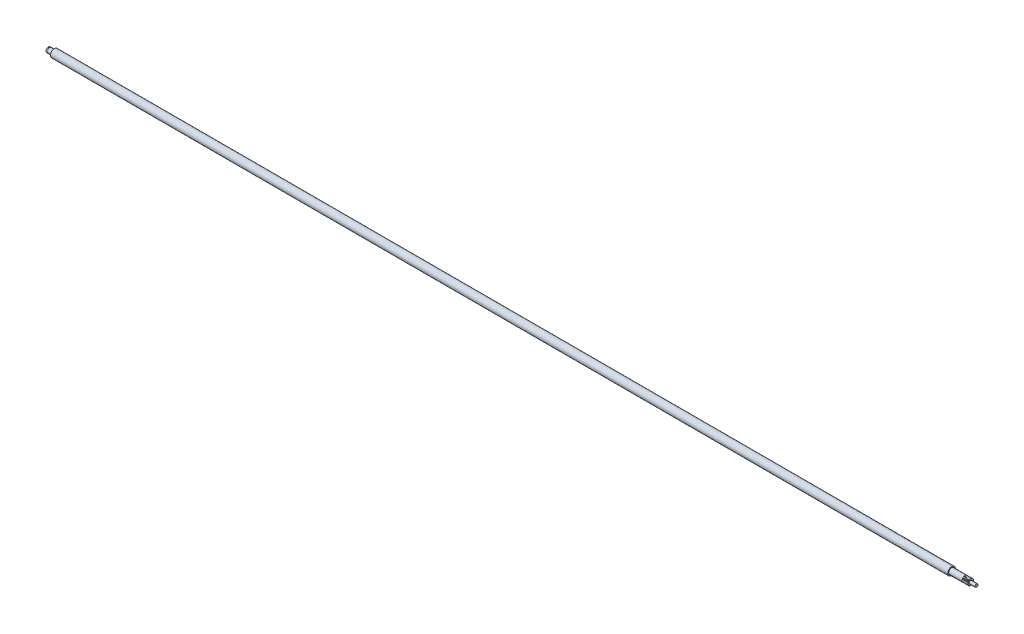
SolidWorks part; units mm, degrees
material "Хромистая нержавеющая сталь"
ref_plane "Спереди" through (0, 0, 0) normal (0, 0, 1) x (1, 0, 0)
ref_plane "Сверху" through (0, 0, 0) normal (0, 1, 0) x (1, 0, 0)
ref_plane "Справа" through (0, 0, 0) normal (1, 0, 0) x (0, 0, -1)
sketch "Эскиз1" plane through (0, 0, 0) normal (0, 0, 1) x (1, 0, 0)
  line L0 (-1813.0019, 5.9419) -> (-1813.0019, 10.9419)
  line L1 (-1813.0019, 10.9419) -> (-1811.3019, 10.9419)
  line L2 (-1811.3019, 10.9419) -> (-1811.3019, 10.7419)
  line L3 (-1811.3019, 10.7419) -> (-1810.1519, 10.7419)
  line L4 (-1810.1519, 10.7419) -> (-1810.1519, 10.9419)
  line L5 (-1810.1519, 10.9419) -> (-1801.0019, 10.9419)
  line L6 (-1801.0019, 10.9419) -> (-1801.0019, 13.9419)
  line L7 (-1801.0019, 13.9419) -> (35.9981, 13.9419)
  line L8 (35.9981, 13.9419) -> (35.9981, 11.9419)
  line L9 (35.9981, 11.9419) -> (74.9981, 11.9419)
  line L10 (74.9981, 11.9419) -> (74.9981, 8.9419)
  line L11 (74.9981, 8.9419) -> (86.9981, 8.9419)
  line L12 (86.9981, 8.9419) -> (86.9981, 5.9419)
  line L13 (86.9981, 5.9419) -> (-1813.0019, 5.9419)
  line L14 (62.9981, 14.6846) -> (62.9981, -1.3142) construction
  dimension "D1" = 1.15
  dimension "D2" = 9.15
  dimension "D3" = 12
  dimension "D4" = 39
  dimension "D5" = 51
  dimension "D6" = 12
  dimension "D7" = 3
  dimension "D8" = 3
  dimension "D9" = 2
  dimension "D10" = 5
  dimension "D11" = 4.8
  dimension "D12" = 5
  dimension "D13" = 1900
revolve "Повернуть1" add sketch "Эскиз1" angle 360 about L13
ref_plane "Плоскость1" through (45.9981, 0, 0) normal (1, 0, 0) x (0, 0, -1)
sketch "Эскиз2" plane through (45.9981, 0, 0) normal (1, 0, 0) x (0, 0, -1)
  circle A0 centre (0, 5.9419) radius 8 construction
  circle A1 centre (0, 5.9419) radius 8
curve "Спираль1" pitch 5 height 290 turns 58
sketch "Эскиз3" plane through (0, 0, 0) normal (0, 0, 1) x (1, 0, 0)
  line L0 (-207.8405, -2.5666) -> (-201.4949, -2.5666) construction
  line L1 (-210.2778, -2.0666) -> (-203.5838, -2.0666) construction
  line L2 (-207.8405, -4.8575) -> (-207.8405, -1.8666) construction
  line L3 (-205.3405, -4.8575) -> (-205.3405, -0.2923) construction
  line L4 (-205.3405, -1.8666) -> (-205.4905, -2.0666)
  line L5 (-205.4905, -2.0666) -> (-205.4905, -2.5666)
  line L6 (-205.4905, -2.5666) -> (-205.1905, -2.5666)
  line L7 (-205.1905, -2.5666) -> (-205.1905, -2.0666)
  line L8 (-205.1905, -2.0666) -> (-205.3405, -1.8666)
  circle A0 centre (-207.8405, -2.5666) radius 1.5875
  point P7 (-207.7498, -2.0666)
  dimension "D1" = 3.175
  dimension "D2" = 0.5
  dimension "D3" = 2.5
  dimension "D4" = 0.2
  dimension "D5" = 0.3
ref_plane "Плоскость2" through (84.9981, 0, 0) normal (1, 0, 0) x (0, 0, -1)
sketch "Эскиз4" plane through (84.9981, 0, 0) normal (1, 0, 0) x (0, 0, -1)
  circle A0 centre (0, 5.9419) radius 6 construction
  circle A1 centre (0, 5.9419) radius 6
curve "Спираль2" pitch 1 height 22 radius 6 centre (84.9981, 5.9419, 0) axis (-1, 0, 0) start towards (0, 0, 1)
sketch "Эскиз5" plane through (0, 0, 0) normal (0, 0, 1) x (1, 0, 0)
  line L0 (76.2561, 0.4419) -> (75.7561, -0.0581)
  line L1 (35.9981, -0.0581) -> (74.9981, -0.0581) construction
  line L2 (75.7561, -0.0581) -> (75.7561, -1.0581)
  line L3 (75.7561, -1.0581) -> (76.7561, -1.0581)
  line L4 (76.7561, -1.0581) -> (76.7561, -0.0581)
  line L5 (76.7561, -0.0581) -> (76.2561, 0.4419)
  line L6 (76.2561, 0.4419) -> (76.2561, -0.2584) construction
  line L7 (75.7561, -0.0581) -> (76.7561, -0.0581) construction
  dimension "D1" = 0.5
  dimension "D2" = 1
  dimension "D3" = 1
sweep "Вырез-По траектории7" cut profiles "Эскиз5" path "Спираль2" align with end faces yes
